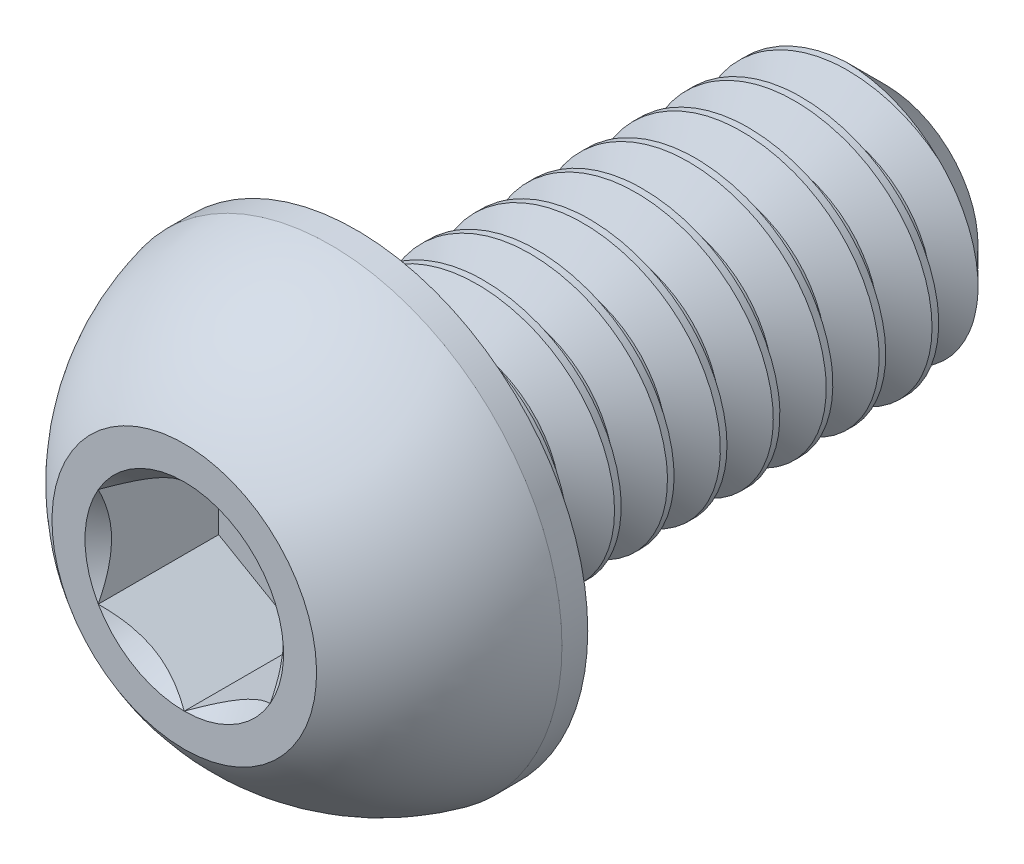
SolidWorks part; units mm, degrees
note: '?' marks a value the reader was unsure of.
ref_plane "Front" through (0, 0, 0) normal (0, 0, 1) x (1, 0, 0)
ref_plane "Top" through (0, 0, 0) normal (0, 1, 0) x (1, 0, 0)
ref_plane "Right" through (0, 0, 0) normal (1, 0, 0) x (0, 0, -1)
sketch "Sketch1" plane through (0, 0, 0) normal (1, 0, 0) x (0, 0, -1)
  line L2 (1.3, 1) -> (5.3, 1)
  line L3 (5.3, 1) -> (5.3, 0)
  line L4 (5.3, 0) -> (1.3, 0)
  line L6 (1.105, 1.75) -> (1.3, 1.75) construction
  line L7 (5.3, 1) -> (5.3, -1) construction
  line L8 (0, 0) -> (1.3, 0) construction
  line L9 (1.3, 1.75) -> (1.3, -1.75) construction
  line L11 (1.3, 1) -> (1.3, 0)
  line L13 (0, 0.65) -> (0, -0.65) construction
  line L14 (0, 0.65) -> (0, 1) construction
  arc A3 (0, 1) -> (1.105, 1.75) centre (1.4858, 0) cw construction
  dimension "D1" = 0.195
revolve "Revolve1" add sketch "Sketch1" angle 360 mid plane about L4
sketch "Sketch3" plane through (0, 0, -5.3) normal (0, 0, -1) x (-1, 0, 0)
  circle A0 centre (0, 0) radius 1
curve "Helix/Spiral1" pitch 0.4 height 4.4 turns 11
chamfer "Chamfer1" distance 0.3 angle 45 1 edges at (0, 1, -5.3)
sketch "Sketch7" plane through (0, 0, 0) normal (1, 0, 0) x (0, 0, -1)
  line L6 (1.105, 1.75) -> (1.3, 1.75) construction
  line L8 (0, 0) -> (1.3, 0) construction
  line L11 (1.3, 1.75) -> (1.3, -1.75) construction
  line L12 (1.105, 1.75) -> (1.3, 1.75)
  line L13 (0, 0) -> (1.3, 0)
  line L14 (0, 0.65) -> (0, -0.65) construction
  line L15 (1.3, 1.75) -> (1.3, 0)
  line L16 (0, 1) -> (0, 0)
  arc A2 (1.105, 1.75) -> (0, 1) centre (1.4858, 0) ccw construction
  arc A3 (1.105, 1.75) -> (0, 1) centre (1.4858, 0) ccw
revolve "Revolve2" add sketch "Sketch7" angle 360 mid plane about L13
sketch "Sketch5" plane through (0, 0, 0) normal (0, 0, 1) x (1, 0, 0)
  line L1 (0.65, -0.3753) -> (0.65, 0.3753)
  line L2 (0.65, 0.3753) -> (0, 0.7506)
  line L3 (0, 0.7506) -> (-0.65, 0.3753)
  line L4 (-0.65, 0.3753) -> (-0.65, -0.3753)
  line L5 (-0.65, -0.3753) -> (0, -0.7506)
  line L6 (0, -0.7506) -> (0.65, -0.3753)
  circle A0 centre (0, 0) radius 0.65 construction
extrude "Cut-Extrude2" cut sketch "Sketch5" against normal blind 0.91
sketch "Sketch6" plane through (0, 0, 0) normal (0, 0, 1) x (1, 0, 0)
  circle A0 centre (0, 0) radius 0.7506
extrude "Cut-Extrude3" cut sketch "Sketch6" against normal blind 0.91 draft 45
sketch "Sketch2" plane through (0, 0, 0) normal (1, 0, 0) x (0, 0, -1)
  line L0 (5, 1) -> (5.35, 1)
  line L1 (5.35, 1) -> (5.2, 0.7402)
  line L2 (5.2, 0.7402) -> (5.15, 0.7402)
  line L3 (5.15, 0.7402) -> (5, 1)
  line L4 (5.075, 0.8701) -> (5.275, 0.8701) construction
  dimension "D1" = 60
  dimension "D2" = 0.05
  dimension "D3" = 0.2
sweep "Cut-Sweep1" cut profiles "Sketch2" path "Helix/Spiral1"
sketch "Sketch10" plane through (0, 0, 0) normal (1, 0, 0) x (0, 0, -1)
  line L0 (5.3, 1) -> (5.3, -1) construction
  point P0 (4.7, -1)
  dimension "D1" = 0.6
ref_axis "Center Axis 1" through (0, 0, -8.1113) along (0, 0, 1)?
ref_plane "Contact Plane 1" through (0, 0, -1.3) normal (0, 0, -1) x (-1, 0, 0)
ref_plane "Contact Plane 2" through (0, 0, 0) normal (0, 0, 1) x (1, 0, 0)
equation "\"D3@Helix/Spiral1\" = \"Lg@Sketch1\" + \"D4@Helix/Spiral1\""
equation "\"D2@Sketch2\" = \"D4@Helix/Spiral1\" * .125"
equation "\"D3@Sketch2\" = \"D4@Helix/Spiral1\" * .5"
equation "\"D1@Chamfer1\" = \"D4@Helix/Spiral1\" * .75"
equation "\"D1@Cut-Extrude2\" = \"Head Ht@Sketch1\" * .7"
equation "\"D1@Sketch1\" = \"Head Ht@Sketch1\" * .15"
equation "\"D1@Sketch10\" = \"D4@Helix/Spiral1\" * 1.5"
equation "\"D1@Cut-Extrude3\" = \"D1@Cut-Extrude2\""
